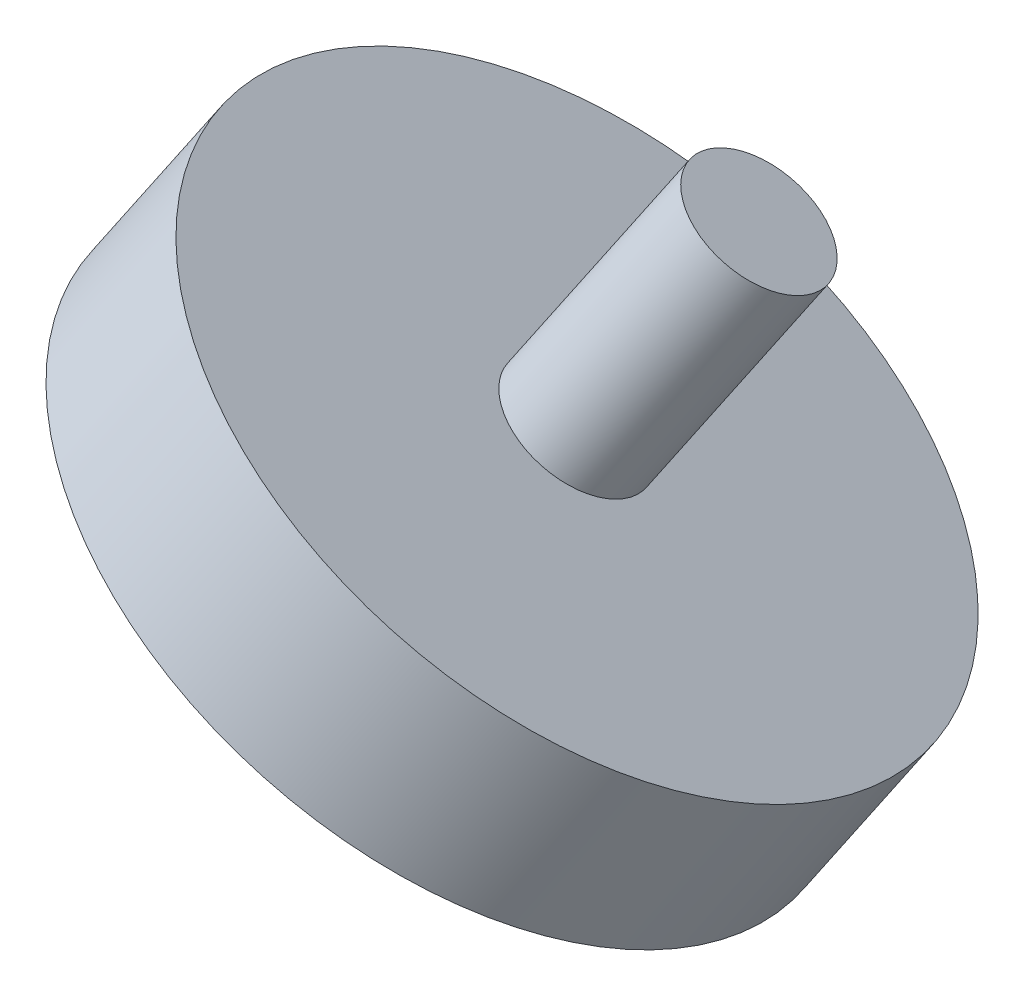
SolidWorks part; units mm, degrees
ref_plane "Front Plane" through (0, 0, 0) normal (0, 0, 1) x (1, 0, 0)
ref_plane "Top Plane" through (0, 0, 0) normal (0, 1, 0) x (1, 0, 0)
ref_plane "Right Plane" through (0, 0, 0) normal (1, 0, 0) x (0, 0, -1)
sketch "Sketch1" plane through (-109.4345, -193.4529, 69.6849) normal (0.4698, 0.8305, -0.2992) x (0.8794, -0.4698, 0.0768)
  circle A0 centre (52.9877, -483.5449) radius 10
extrude "Boss-Extrude1" add sketch "Sketch1" along normal blind 5
sketch "Sketch2" plane through (-107.0854, -189.3003, 68.189) normal (0.4698, 0.8305, -0.2992) x (0.8794, -0.4698, 0.0768)
  circle A0 centre (52.9877, -483.5449) radius 1.95
extrude "Boss-Extrude2" add sketch "Sketch2" along normal blind 7 contours A0
